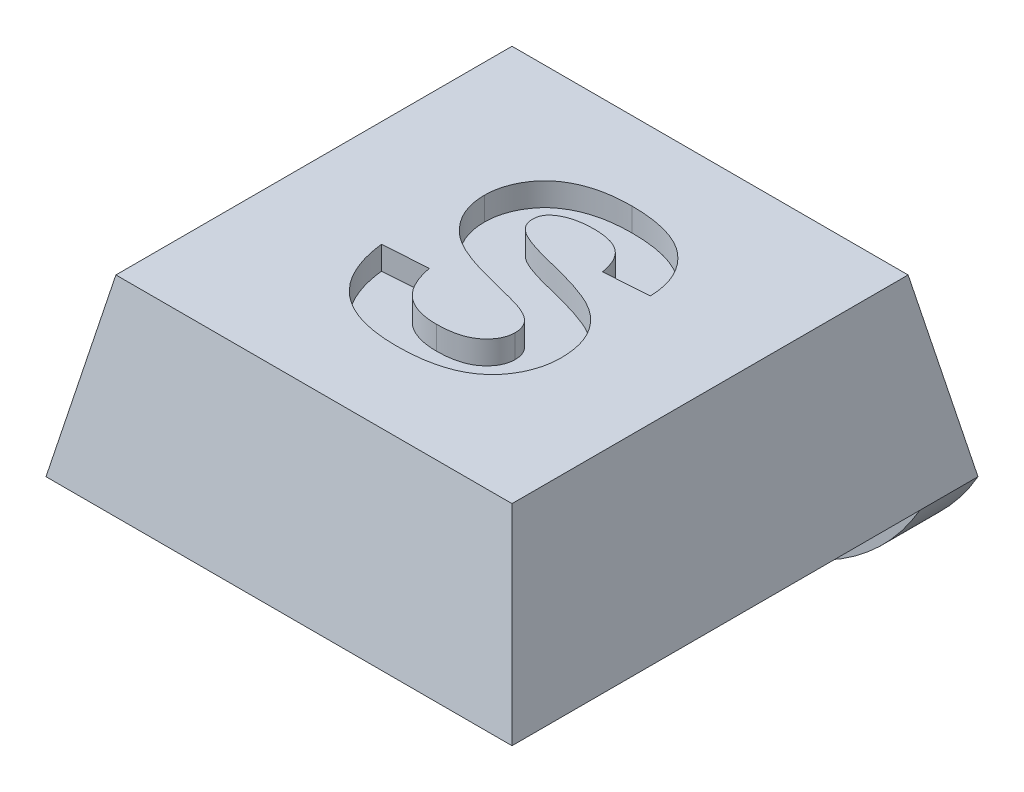
SolidWorks part; units mm, degrees
ref_plane "Front Plane" through (0, 0, 0) normal (0, 0, 1) x (1, 0, 0)
ref_plane "Top Plane" through (0, 0, 0) normal (0, 1, 0) x (1, 0, 0)
ref_plane "Right Plane" through (0, 0, 0) normal (1, 0, 0) x (0, 0, -1)
sketch "Sketch1" plane through (0, 0, 0) normal (0, 1, 0) x (1, 0, 0)
  line L1 (0, 0) -> (8, 0)
  line L2 (0, 0) -> (0, 8)
  line L3 (0, 8) -> (8, 8)
  line L4 (8, 0) -> (8, 8)
  dimension "D1" = 8
  dimension "D2" = 8
extrude "Boss-Extrude1" add sketch "Sketch1" along normal blind 3
sketch "Sketch2" plane through (0, 0, 0) normal (0, 0, 1) x (1, 0, 0)
  line L0 (0, 0) -> (0.6, 3)
  line L1 (0, 3) -> (8, 3) construction
  line L2 (0.6, 3) -> (0, 3)
  line L3 (0, 3) -> (0, 0)
  line L4 (8, 0) -> (7.4, 3)
  line L5 (7.4, 3) -> (8, 3)
  line L6 (8, 3) -> (8, 0)
  dimension "D1" = 0.6
  dimension "D2" = 0.6
extrude "Cut-Extrude1" cut sketch "Sketch2" against normal through all both and the other way through all
sketch "Sketch3" plane through (0, 0, 0) normal (1, 0, 0) x (0, 0, -1)
  line L0 (0, 0) -> (0.6, 3)
  line L1 (8, 3) -> (0, 3) construction
  line L2 (0.6, 3) -> (0, 3)
  line L3 (0, 3) -> (0, 0)
  line L4 (8, 3) -> (7.4, 3)
  line L5 (7.4, 3) -> (8, 0)
  line L6 (8, 3) -> (8, 0)
  dimension "D1" = 0.6
  dimension "D2" = 0.6
extrude "Cut-Extrude2" cut sketch "Sketch3" along normal blind 11
sketch "Sketch4" plane through (0, 0, 0) normal (0, -1, 0) x (1, 0, 0)
  line L0 (8, 0) -> (8, -8) construction
  line L3 (0, 0) -> (8, 0) construction
  circle A0 centre (4, -3.75) radius 1.8
  dimension "D1" = 3.6
  dimension "D2" = 4
  dimension "D3" = 3.75
extrude "Cut-Extrude3" cut sketch "Sketch4" against normal blind 0.8
sketch "Sketch5" plane through (0, 0, 0) normal (0, -1, 0) x (1, 0, 0)
  line L0 (8, 0) -> (8, -8) construction
  line L1 (0, -8) -> (8, -8)
  line L2 (0, -8) -> (0, -7)
  line L3 (0, -7) -> (8, -7)
  line L4 (8, -8) -> (8, -7)
  dimension "D1" = 1
extrude "Boss-Extrude2" add sketch "Sketch5" along normal blind 2
fillet "Fillet1" radius 4 2 edges at (8, -2, -7.5) (0, -2, -7.5)
sketch "Sketch6" plane through (0, 3, 0) normal (0, 1, 0) x (1, 0, 0)
  text T0 "S" font "Arial" height 4
extrude "Cut-Extrude4" cut sketch "Sketch6" against normal blind 0.4
